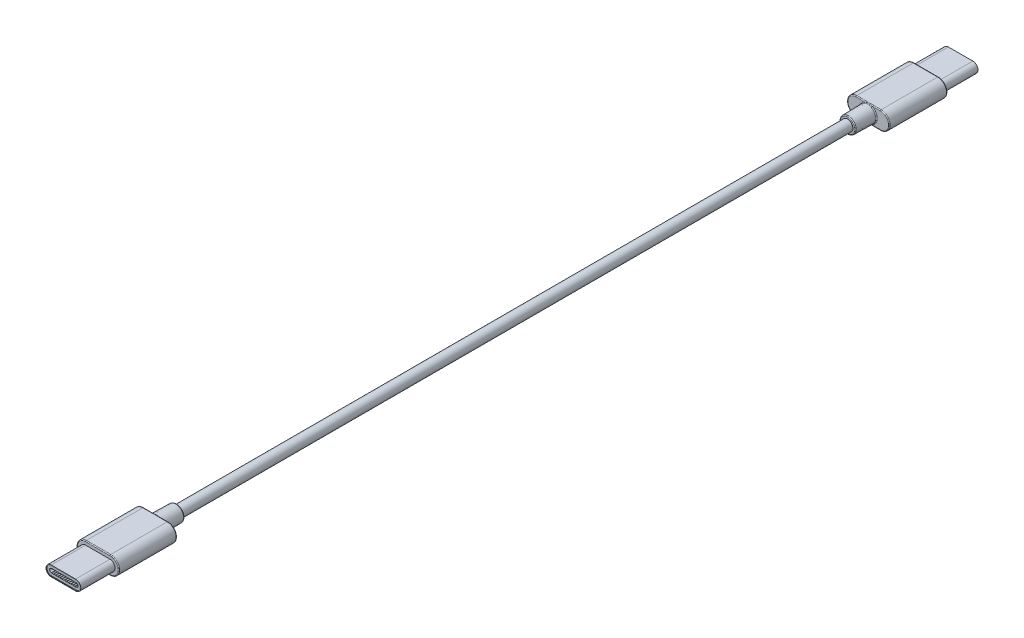
SolidWorks part; units mm, degrees
ref_plane "Спереди" through (0, 0, 0) normal (0, 0, 1) x (1, 0, 0)
ref_plane "Сверху" through (0, 0, 0) normal (0, 1, 0) x (1, 0, 0)
ref_plane "Справа" through (0, 0, 0) normal (1, 0, 0) x (0, 0, -1)
sketch "Эскиз1" plane through (0, 0, 0) normal (0, 0, 1) x (1, 0, 0)
  line L0 (-9.3749, 0) -> (11.4784, 0) construction
  line L1 (0, 4.8728) -> (0, -5.3518) construction
  line L2 (2.95, 0) -> (-2.95, 0) construction
  line L3 (2.95, -1.25) -> (-2.95, -1.25)
  line L4 (2.95, 1.25) -> (-2.95, 1.25)
  line L5 (-2.95, 0) -> (2.95, 0) construction
  line L6 (-2.95, 1.1) -> (2.95, 1.1)
  line L7 (-2.95, -1.1) -> (2.95, -1.1)
  arc A0 (2.95, -1.25) -> (2.95, 1.25) centre (2.95, 0) ccw
  arc A1 (-2.95, 1.25) -> (-2.95, -1.25) centre (-2.95, 0) ccw
  arc A2 (-2.95, 1.1) -> (-2.95, -1.1) centre (-2.95, 0) ccw
  arc A3 (2.95, -1.1) -> (2.95, 1.1) centre (2.95, 0) ccw
  point P7 (0, 0)
  point P12 (-4.2, 0)
  point P13 (4.2, 0)
  point P16 (0, 0)
  dimension "D1" = 1.25
  dimension "D4" = 0.15
  dimension "D2" = 5.9
  dimension "D3" = 8.4
extrude "Бобышка-Вытянуть1" add sketch "Эскиз1" along normal blind 8.3
sketch "Эскиз2" plane through (0, 0, 0) normal (0, 0, 1) x (1, 0, 0)
  line L0 (-2.95, 1.1) -> (2.95, 1.1) construction
  line L1 (-2.95, 1.1) -> (2.95, 1.1)
  line L2 (-2.95, -1.1) -> (2.95, -1.1) construction
  line L3 (-2.95, -1.1) -> (2.95, -1.1)
  line L4 (3, 0) -> (-3, 0) construction
  line L7 (-9.3749, 0) -> (11.4784, 0) construction
  line L8 (3, -0.44) -> (-3, -0.44)
  line L9 (3, 0.44) -> (-3, 0.44)
  arc A0 (-2.95, 1.1) -> (-2.95, -1.1) centre (-2.95, 0) ccw construction
  arc A1 (-2.95, 1.1) -> (-2.95, -1.1) centre (-2.95, 0) ccw
  arc A2 (2.95, -1.1) -> (2.95, 1.1) centre (2.95, 0) ccw construction
  arc A3 (2.95, -1.1) -> (2.95, 1.1) centre (2.95, 0) ccw
  arc A6 (3, -0.44) -> (3, 0.44) centre (3, 0) ccw
  arc A7 (-3, 0.44) -> (-3, -0.44) centre (-3, 0) ccw
  point P10 (0, 0)
  dimension "D1" = 6
  dimension "D2" = 0.66
extrude "Бобышка-Вытянуть2" add sketch "Эскиз2" along normal offset from surface (8.2 mm away) 0.1 up to face at (0, 0, 8.3)
sketch "Эскиз3" plane through (0, 0, 8.2) normal (0, 0, 1) x (1, 0, 0)
  line L0 (0, 1.9476) -> (0, -1.6285) construction
  line L1 (-4.5756, 0) -> (4.7742, 0) construction
  line L2 (-3.01, -0.5) -> (-3.01, 0.5)
  line L3 (-3.01, 0.5) -> (-2.71, 0.5)
  line L4 (-2.71, 0.5) -> (-2.71, -0.5)
  line L5 (-3.01, -0.5) -> (-2.71, -0.5)
  line L6 (-2.49, 0.5) -> (-2.19, 0.5)
  line L7 (-2.19, 0.5) -> (-2.19, -0.5)
  line L8 (-2.49, -0.5) -> (-2.49, 0.5)
  line L9 (-2.49, -0.5) -> (-2.19, -0.5)
  line L10 (-1.97, 0.5) -> (-1.67, 0.5)
  line L11 (-1.67, 0.5) -> (-1.67, -0.5)
  line L12 (-1.97, -0.5) -> (-1.97, 0.5)
  line L13 (-1.97, -0.5) -> (-1.67, -0.5)
  line L14 (-1.45, 0.5) -> (-1.15, 0.5)
  line L15 (-1.15, 0.5) -> (-1.15, -0.5)
  line L16 (-1.45, -0.5) -> (-1.45, 0.5)
  line L17 (-1.45, -0.5) -> (-1.15, -0.5)
  line L18 (-0.93, 0.5) -> (-0.63, 0.5)
  line L19 (-0.63, 0.5) -> (-0.63, -0.5)
  line L20 (-0.93, -0.5) -> (-0.93, 0.5)
  line L21 (-0.93, -0.5) -> (-0.63, -0.5)
  line L22 (-0.41, 0.5) -> (-0.11, 0.5)
  line L23 (-0.11, 0.5) -> (-0.11, -0.5)
  line L24 (-0.41, -0.5) -> (-0.41, 0.5)
  line L25 (-0.41, -0.5) -> (-0.11, -0.5)
  line L26 (0.11, 0.5) -> (0.41, 0.5)
  line L27 (0.41, 0.5) -> (0.41, -0.5)
  line L28 (0.11, -0.5) -> (0.11, 0.5)
  line L29 (0.11, -0.5) -> (0.41, -0.5)
  line L30 (0.63, 0.5) -> (0.93, 0.5)
  line L31 (0.93, 0.5) -> (0.93, -0.5)
  line L32 (0.63, -0.5) -> (0.63, 0.5)
  line L33 (0.63, -0.5) -> (0.93, -0.5)
  line L34 (1.15, 0.5) -> (1.45, 0.5)
  line L35 (1.45, 0.5) -> (1.45, -0.5)
  line L36 (1.15, -0.5) -> (1.15, 0.5)
  line L37 (1.15, -0.5) -> (1.45, -0.5)
  line L38 (1.67, 0.5) -> (1.97, 0.5)
  line L39 (1.97, 0.5) -> (1.97, -0.5)
  line L40 (1.67, -0.5) -> (1.67, 0.5)
  line L41 (1.67, -0.5) -> (1.97, -0.5)
  line L42 (2.19, 0.5) -> (2.49, 0.5)
  line L43 (2.49, 0.5) -> (2.49, -0.5)
  line L44 (2.19, -0.5) -> (2.19, 0.5)
  line L45 (2.19, -0.5) -> (2.49, -0.5)
  line L46 (2.71, 0.5) -> (3.01, 0.5)
  line L47 (3.01, 0.5) -> (3.01, -0.5)
  line L48 (2.71, -0.5) -> (2.71, 0.5)
  line L49 (2.71, -0.5) -> (3.01, -0.5)
  point P10 (-2.71, 0)
  point P11 (-3.01, 0)
  dimension "D1" = 1
  dimension "D2" = 0.3
  dimension "D3" = 3.01
  dimension "D5" = 0.52
  dimension "D4" = 12
extrude "Вырез-Вытянуть1" cut sketch "Эскиз3" against normal up to surface (8.2 mm away) up to face at (0, 0, 0)
sketch "Эскиз4" plane through (0, 0, 0) normal (0, 0, 1) x (1, 0, 0)
  line L0 (-2.95, 0) -> (2.95, 0) construction
  line L1 (-2.95, 2.15) -> (2.95, 2.15)
  line L2 (-2.95, -2.15) -> (2.95, -2.15)
  arc A0 (-2.95, 2.15) -> (-2.95, -2.15) centre (-2.95, 0) ccw
  arc A1 (2.95, -2.15) -> (2.95, 2.15) centre (2.95, 0) ccw
  arc A2 (-2.95, 1.25) -> (-2.95, -1.25) centre (-2.95, 0) ccw construction
  point P4 (0, 0)
  dimension "D1" = 0.9
extrude "Бобышка-Вытянуть3" add sketch "Эскиз4" against normal blind 14
sketch "Эскиз5" plane through (0, 0, -14) normal (0, 0, -1) x (-1, 0, 0)
  circle A0 centre (0, 0) radius 2
  dimension "D1" = 4
extrude "Бобышка-Вытянуть4" add sketch "Эскиз5" along normal blind 5 draft 1
fillet "Скругление1" radius 0.2 9 edges at (5.1, 0, -14) (0, -2.15, -14) (-5.1, 0, -14) (5.1, 0, 0) (0, -2.15, 0) (-5.1, 0, 0) (0, 2.15, -14) (0, 2.15, 0) (-1.9127, 0, -19)
fillet "Скругление3" radius 0.2 4 edges at (0, 2, -14) (-2, 0, -14) (0, -2, -14) (2, 0, -14)
ref_plane "Плоскость1" through (0, 0, -100) normal (0, 0, 1) x (1, 0, 0)
mirror "Зеркальное отражение2" about plane through (0, 0, -100) normal (0, 0, 1) of bodies 107
sketch "Эскиз6" plane through (0, 0, 0) normal (0, 1, 0) x (1, 0, 0)
  line L0 (0, -10.6469) -> (0, 19) construction
  line L1 (1.7162, 19) -> (-1.7162, 19) construction
  line L2 (0, 19) -> (0, 181.1965)
  line L3 (1.9162, 181.1965) -> (-1.9162, 181.1965) construction
sketch "Эскиз7" plane through (0, 0, -19) normal (0, 0, -1) x (-1, 0, 0)
  circle A0 centre (0, 0) radius 1.3
  dimension "D1" = 2.6
sweep "По траектории1" add profiles "Эскиз7" path "Эскиз6"
